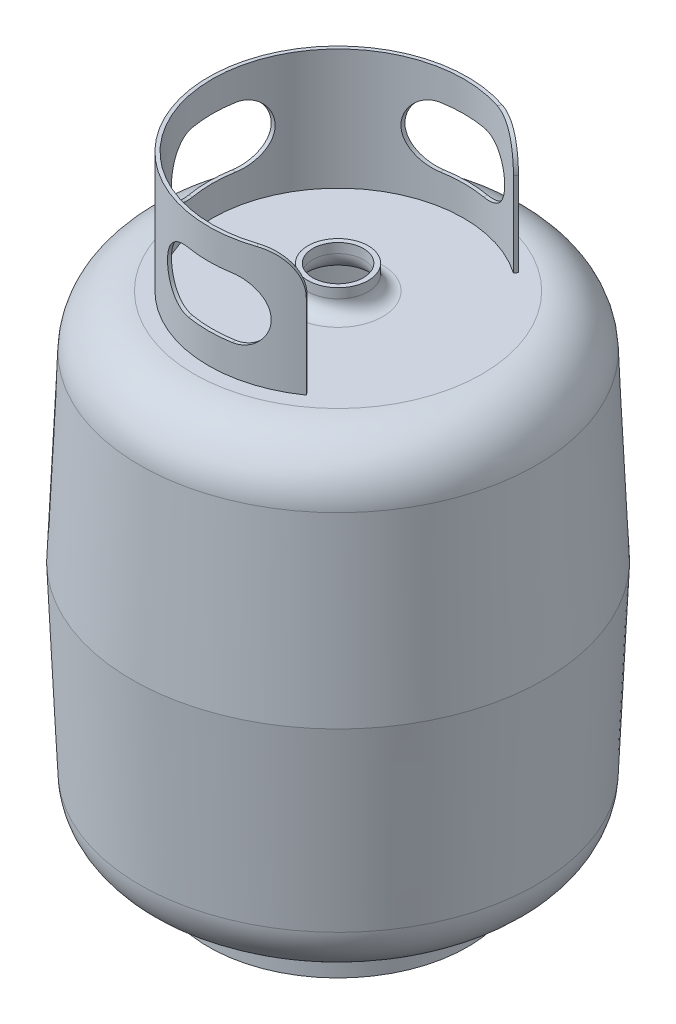
SolidWorks part; units mm, degrees
material "1060 Alloy"
ref_plane "Front Plane" through (0, 0, 0) normal (0, 0, 1) x (1, 0, 0)
ref_plane "Top Plane" through (0, 0, 0) normal (0, 1, 0) x (1, 0, 0)
ref_plane "Right Plane" through (0, 0, 0) normal (1, 0, 0) x (0, 0, -1)
sketch "Sketch1" plane through (0, 0, 0) normal (1, 0, 0) x (0, 0, -1)
  line L0 (0, 0) -> (0, 407.5) construction
  line L1 (0, 0) -> (119.4219, 0)
  line L2 (164.379, 43.0371) -> (170.9593, 193.75)
  line L3 (170.9593, 193.75) -> (164.379, 344.4629)
  line L4 (119.4219, 387.5) -> (37, 387.5)
  line L5 (25, 399.5) -> (25, 407.5)
  line L6 (25, 407.5) -> (0, 407.5)
  line L7 (0, 4) -> (119.4219, 4)
  line L8 (160.3828, 43.2116) -> (166.9555, 193.75)
  line L9 (166.9555, 193.75) -> (160.3828, 344.2884)
  line L10 (119.4219, 383.5) -> (37, 383.5)
  line L11 (21, 399.5) -> (21, 403.5)
  line L12 (21, 403.5) -> (0, 403.5)
  line L13 (0, 407.5) -> (0, 403.5)
  line L14 (0, 4) -> (0, 0)
  arc A0 (37, 387.5) -> (25, 399.5) centre (37, 399.5) cw
  arc A1 (119.4219, 0) -> (164.379, 43.0371) centre (119.4219, 45) ccw
  arc A2 (164.379, 344.4629) -> (119.4219, 387.5) centre (119.4219, 342.5) ccw
  arc A3 (119.4219, 4) -> (160.3828, 43.2116) centre (119.4219, 45) ccw
  arc A4 (160.3828, 344.2884) -> (119.4219, 383.5) centre (119.4219, 342.5) ccw
  arc A5 (37, 383.5) -> (21, 399.5) centre (37, 399.5) cw
  point P10 (25, 387.5)
  point P13 (162.5, 0)
  point P16 (162.5, 387.5)
  dimension "D8" = 12
  dimension "D9" = 45
  dimension "D1" = 325
  dimension "D2" = 325
  dimension "D3" = 387.5
  dimension "D4" = 50
  dimension "D5" = 20
  dimension "D6" = 92.5
  dimension "D7" = 92.5
  dimension "D10" = 4
revolve "Revolve1" add sketch "Sketch1" angle 360 about L0
sketch "Sketch2" plane through (0, 407.5, 0) normal (0, 1, 0) x (1, 0, 0)
  circle A0 centre (0, 0) radius 21
  dimension "D1" = 42
extrude "Cut-Extrude1" cut sketch "Sketch2" against normal blind 34
sketch "Sketch3" plane through (0, 387.5, 0) normal (0, 1, 0) x (1, 0, 0)
  line L0 (0, -138.194) -> (0, 149.2495) construction
  line L1 (-144.1523, 0) -> (167.7544, 0) construction
  line L2 (0, 0) -> (108.3606, 154.755) construction
  line L3 (0, 0) -> (112.7923, -161.0841) construction
  line L4 (59.8939, -85.5374) -> (61.6147, -87.9948)
  line L5 (59.8939, 85.5374) -> (61.6147, 87.9948)
  arc A0 (61.6147, 87.9948) -> (61.6147, -87.9948) centre (0, 0) ccw
  circle A1 centre (0, 0) radius 119.4219
  circle A2 centre (0, 0) radius 119.4219 construction
  arc A3 (59.8939, 85.5374) -> (59.8939, -85.5374) centre (0, 0) ccw
  circle A5 centre (0, 0) radius 104.4219 construction
  circle A6 centre (0, 0) radius 107.4219 construction
  point P12 (102.728, 31.4071)
  point P13 (104.4219, 0)
  dimension "D4" = 12
  dimension "D2" = 55
  dimension "D3" = 55
  dimension "D1" = 0
  dimension "D5" = 3
extrude "Boss-Extrude1" add sketch "Sketch3" along normal blind 100 separate body
fillet "Fillet3" radius 30 1 edges at (60.7543, 487.5, -86.7661)
fillet "Fillet4" radius 30 1 edges at (60.7543, 487.5, 86.7661)
sketch "Sketch5" plane through (0, 0, 0) normal (1, 0, 0) x (0, 0, -1)
  line L0 (0, 363.4907) -> (0, 437.5) construction
  line L1 (0, 487.5) -> (0, 387.5) construction
  line L2 (-104.4219, 387.5) -> (104.4219, 387.5) construction
  line L3 (0, 437.5) -> (-18, 437.5) construction
  line L4 (-18, 437.5) -> (0, 437.5) construction
  line L5 (0, 437.5) -> (18, 437.5) construction
  line L6 (-18, 437.5) -> (18, 437.5) construction
  line L7 (-18, 462.5) -> (18, 462.5)
  line L8 (-18, 412.5) -> (18, 412.5)
  arc A0 (-18, 462.5) -> (-18, 412.5) centre (-18, 437.5) ccw
  arc A1 (18, 412.5) -> (18, 462.5) centre (18, 437.5) ccw
  point P7 (0, 437.5)
  dimension "D1" = 50
  dimension "D2" = 18
  dimension "D3" = 18
  dimension "D4" = 50
extrude "Cut-Extrude2" cut sketch "Sketch5" against normal through all
sketch "Sketch6" plane through (0, 0, 0) normal (0, 0, 1) x (1, 0, 0)
  line L0 (0, 352.753) -> (0, 437.5) construction
  line L1 (-107.4219, 387.5) -> (61.6147, 387.5) construction
  line L2 (0, 437.5) -> (-18, 437.5) construction
  line L3 (0, 437.5) -> (18, 437.5) construction
  line L4 (-18, 437.5) -> (18, 437.5) construction
  line L5 (-18, 462.5) -> (18, 462.5)
  line L6 (-18, 412.5) -> (18, 412.5)
  arc A0 (-18, 462.5) -> (-18, 412.5) centre (-18, 437.5) ccw
  arc A1 (18, 412.5) -> (18, 462.5) centre (18, 437.5) ccw
  point P5 (0, 437.5)
  dimension "D1" = 50
  dimension "D2" = 18
  dimension "D3" = 18
  dimension "D4" = 50
extrude "Cut-Extrude3" cut sketch "Sketch6" against normal through all both and the other way through all contours L6 A1 L5 A0
sketch "Sketch7" plane through (0, 0, 0) normal (0, -1, 0) x (1, 0, 0)
  circle A0 centre (0, 0) radius 107.4219
  circle A1 centre (0, 0) radius 119.4219
  circle A2 centre (0, 0) radius 119.4219 construction
  circle A3 centre (0, 0) radius 104.4219
  dimension "D2" = 12
  dimension "D1" = 0
  dimension "D3" = 3
extrude "Boss-Extrude2" add sketch "Sketch7" along normal blind 30
equation "\"a\"= 325mm"
equation "\"b\" = 387.5mm"
equation "\"D1@Sketch1\"=\"a\""
equation "\"D2@Sketch1\"=\"a\""
equation "\"D3@Sketch1\"=\"b\""
